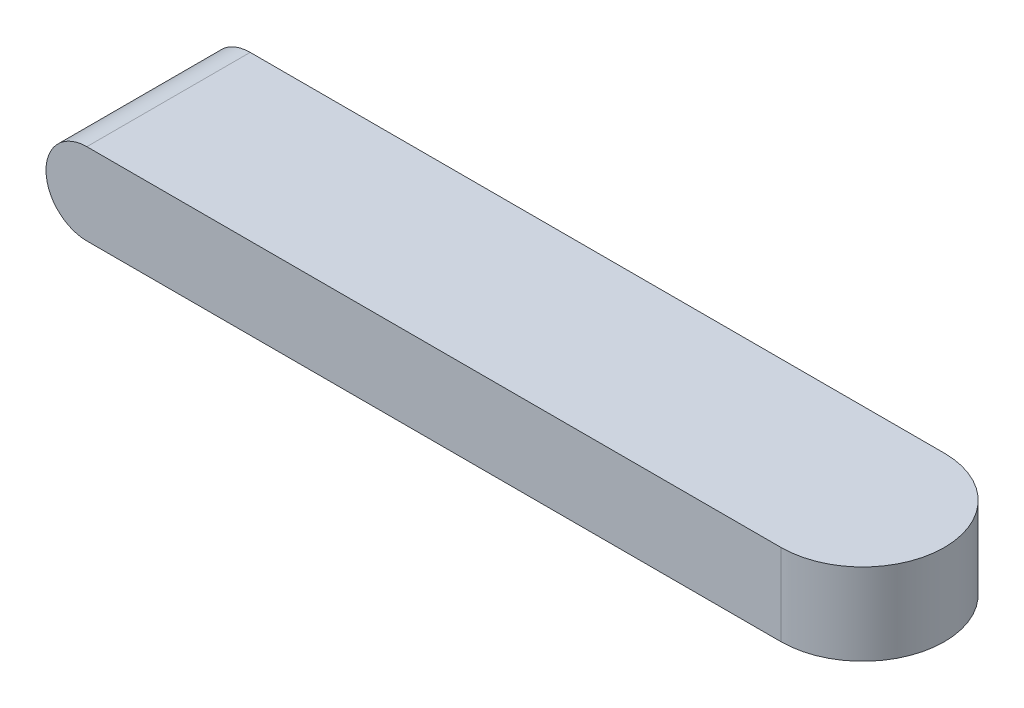
SolidWorks part; units mm, degrees
ref_plane "Front Plane" through (0, 0, 0) normal (0, 0, 1) x (1, 0, 0)
ref_plane "Top Plane" through (0, 0, 0) normal (0, 1, 0) x (1, 0, 0)
ref_plane "Right Plane" through (0, 0, 0) normal (1, 0, 0) x (0, 0, -1)
sketch "Sketch1" plane through (0, 0, 0) normal (0, 0, 1) x (1, 0, 0)
  line L1 (5.1741, -0.7264) -> (-4.8259, -0.7264)
  line L2 (5.1741, -0.7264) -> (5.1741, 0.2736)
  line L3 (5.1741, 0.2736) -> (-4.8259, 0.2736)
  line L4 (-4.8259, -0.7264) -> (-4.8259, 0.2736)
  line L5 (5.1741, -0.7264) -> (-4.8259, 0.2736) construction
  line L6 (5.1741, 0.2736) -> (-4.8259, -0.7264) construction
  point P0 (0.1741, -0.2264)
  dimension "D1" = 10
  dimension "D2" = 1
extrude "Boss-Extrude1" add sketch "Sketch1" along normal blind 2
fillet "Fillet1" 2 edges at (5.1741, -0.2264, 2) (5.1741, -0.2264, 0) type full round first side face at (0.1741, -0.2264, 2) second side face at (0.1741, -0.2264, 0) middle face at (5.1741, -0.2264, 1)
fillet "Fillet2" 2 edges at (-4.8259, 0.2736, 1) (-4.8259, -0.7264, 1) type full round first side face at (-0.0759, 0.2736, 1) second side face at (-0.0759, -0.7264, 1) middle face at (-4.8259, -0.2264, 1)
sketch "Sketch2" plane through (0, 0, 2) normal (0, 0, 1) x (1, 0, 0)
  arc A0 (-4.3259, 0.2736) -> (-4.3259, -0.7264) centre (-4.3259, -0.2264) ccw construction
  point P0 (-4.8259, -0.2264)
  point P1 (-4.8259, -0.2264)
sketch "Sketch3" plane through (0, -0.7264, 0) normal (0, -1, 0) x (1, 0, 0)
  line L0 (-4.3259, 2) -> (-4.3259, 0) construction
  point P0 (-4.3259, 1)
